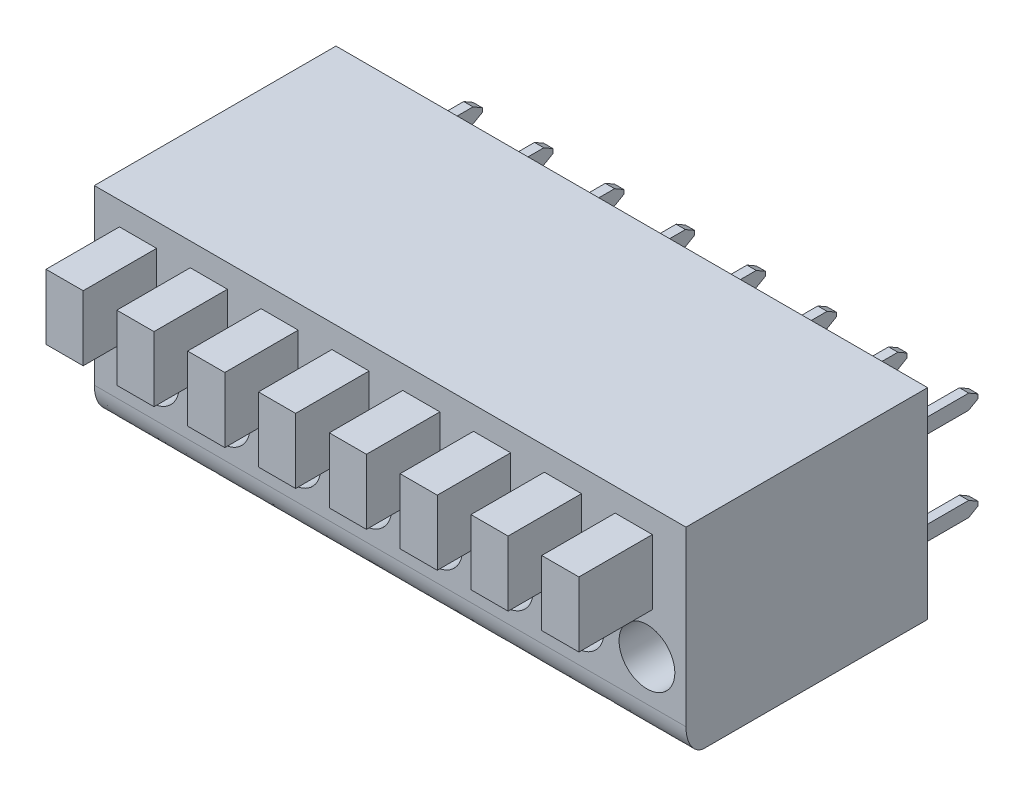
SolidWorks part; units mm, degrees
ref_plane "Спереди" through (0, 0, 0) normal (0, 0, 1) x (1, 0, 0)
ref_plane "Сверху" through (0, 0, 0) normal (0, 1, 0) x (1, 0, 0)
ref_plane "Справа" through (0, 0, 0) normal (1, 0, 0) x (0, 0, -1)
sketch "Эскиз1" plane through (0, 0, 0) normal (0, 0, 1) x (1, 0, 0)
  line L1 (-15.915, -5.4) -> (15.915, -5.4)
  line L2 (-15.915, -5.4) -> (-15.915, 5.4)
  line L3 (-15.915, 5.4) -> (15.915, 5.4)
  line L4 (15.915, -5.4) -> (15.915, 5.4)
  line L5 (-15.915, -5.4) -> (15.915, 5.4) construction
  line L6 (-15.915, 5.4) -> (15.915, -5.4) construction
  point P0 (0, 0)
  dimension "D1" = 31.83
  dimension "D2" = 10.8
extrude "Бобышка-Вытянуть1" add sketch "Эскиз1" along normal blind 13
fillet "Скругление1" radius 1 1 edges at (0, -5.4, 13) second distance 1.5 first distance on face at (0, -5.4, 6.5)
sketch "Эскиз2" plane through (0, 0, 13) normal (0, 0, 1) x (1, 0, 0)
  line L0 (15.915, -3.9) -> (15.915, 5.4) construction
  line L1 (12.105, 0.65) -> (14.105, 0.65)
  line L2 (12.105, 0.65) -> (12.105, 4.15)
  line L3 (12.105, 4.15) -> (14.105, 4.15)
  line L4 (14.105, 0.65) -> (14.105, 4.15)
  line L5 (12.105, 0.65) -> (14.105, 4.15) construction
  line L6 (12.105, 4.15) -> (14.105, 0.65) construction
  line L7 (15.915, 5.4) -> (-15.915, 5.4) construction
  point P0 (13.105, 2.4)
  dimension "D1" = 3.5
  dimension "D2" = 2
  dimension "D3" = 3.81
  dimension "D4" = 4.75
extrude "Бобышка-Вытянуть2" add sketch "Эскиз2" along normal blind 3.95
sketch "Эскиз3" plane through (0, 0, 13) normal (0, 0, 1) x (1, 0, 0)
  line L0 (15.915, -3.9) -> (15.915, 5.4) construction
  circle A0 centre (13.815, -1.686) radius 1.5
  dimension "D1" = 3
  dimension "D2" = 2.1
extrude "Вырез-Вытянуть1" cut sketch "Эскиз3" against normal blind 3.95
sketch "Эскиз4" plane through (0, 0, 0) normal (0, 0, -1) x (-1, 0, 0)
  line L0 (-15.915, 5.4) -> (15.915, 5.4) construction
  line L1 (-15.125, 2.45) -> (-14.625, 2.45)
  line L2 (-15.125, 2.45) -> (-15.125, 3.25)
  line L3 (-15.125, 3.25) -> (-14.625, 3.25)
  line L4 (-14.625, 2.45) -> (-14.625, 3.25)
  line L5 (-15.125, 2.45) -> (-14.625, 3.25) construction
  line L6 (-15.125, 3.25) -> (-14.625, 2.45) construction
  line L7 (-14.625, -1.75) -> (-15.125, -1.75)
  line L8 (-14.625, -1.75) -> (-14.625, -2.55)
  line L9 (-14.625, -2.55) -> (-15.125, -2.55)
  line L10 (-15.125, -1.75) -> (-15.125, -2.55)
  line L11 (-14.625, -1.75) -> (-15.125, -2.55) construction
  line L12 (-14.625, -2.55) -> (-15.125, -1.75) construction
  line L14 (-15.915, -5.4) -> (-15.915, 5.4) construction
  point P0 (-14.875, 2.85)
  point P5 (-14.875, -2.15)
  dimension "D1" = 0.5
  dimension "D2" = 0.8
  dimension "D3" = 5
  dimension "D4" = 2.55
  dimension "D5" = 1.04
extrude "Бобышка-Вытянуть3" add sketch "Эскиз4" along normal blind 3.5
chamfer "Фаска1" distance 0.5 angle 30 4 edges at (14.875, -2.55, -3.5) (14.875, -1.75, -3.5) (14.875, 2.45, -3.5) (14.875, 3.25, -3.5) first distance on face at (14.875, -2.55, -1.75) first distance on face at (14.875, -1.75, -1.75) first distance on face at (14.875, 2.45, -1.75) first distance on face at (14.875, 3.25, -1.75)
pattern_linear "Линейный массив2" count 8 spacing 3.81 along (-1, 0, 0) of "Бобышка-Вытянуть2", "Вырез-Вытянуть1", "Бобышка-Вытянуть3", "Фаска1"
